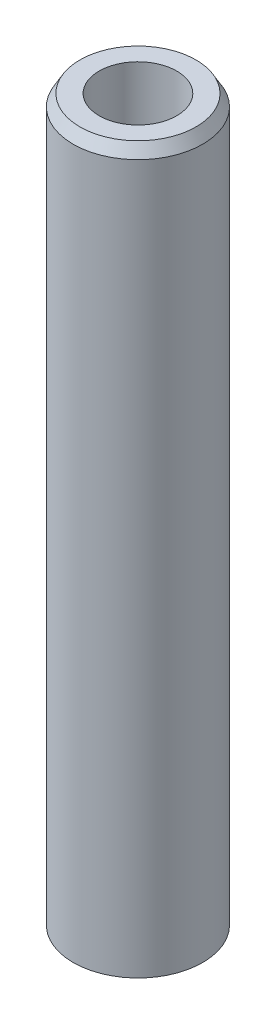
SolidWorks part; units mm, degrees
ref_plane "Front Plane" through (0, 0, 0) normal (0, 0, 1) x (1, 0, 0)
ref_plane "Top Plane" through (0, 0, 0) normal (0, 1, 0) x (1, 0, 0)
ref_plane "Right Plane" through (0, 0, 0) normal (1, 0, 0) x (0, 0, -1)
sketch "Sketch1" plane through (0, 0, 0) normal (0, 1, 0) x (1, 0, 0)
  circle A0 centre (0, 0) radius 30
  dimension "SHAFT_OD" = 60
extrude "Boss-Extrude1" add sketch "Sketch1" along normal blind 336.737
sketch "Sketch2" plane through (0, 0, 0) normal (0, 1, 0) x (1, 0, 0)
  circle A0 centre (0, 0) radius 17.9679
  dimension "BORE_D" = 35.9357
extrude "Cut-Extrude1" cut sketch "Sketch2" along normal through all
chamfer "Chamfer1" distance 5.3895 angle 30 2 edges at (0, 336.737, 30) (0, 0, 30) first distance on face at (0, 336.737, 30) first distance on face at (0, 0, 17.9679)
